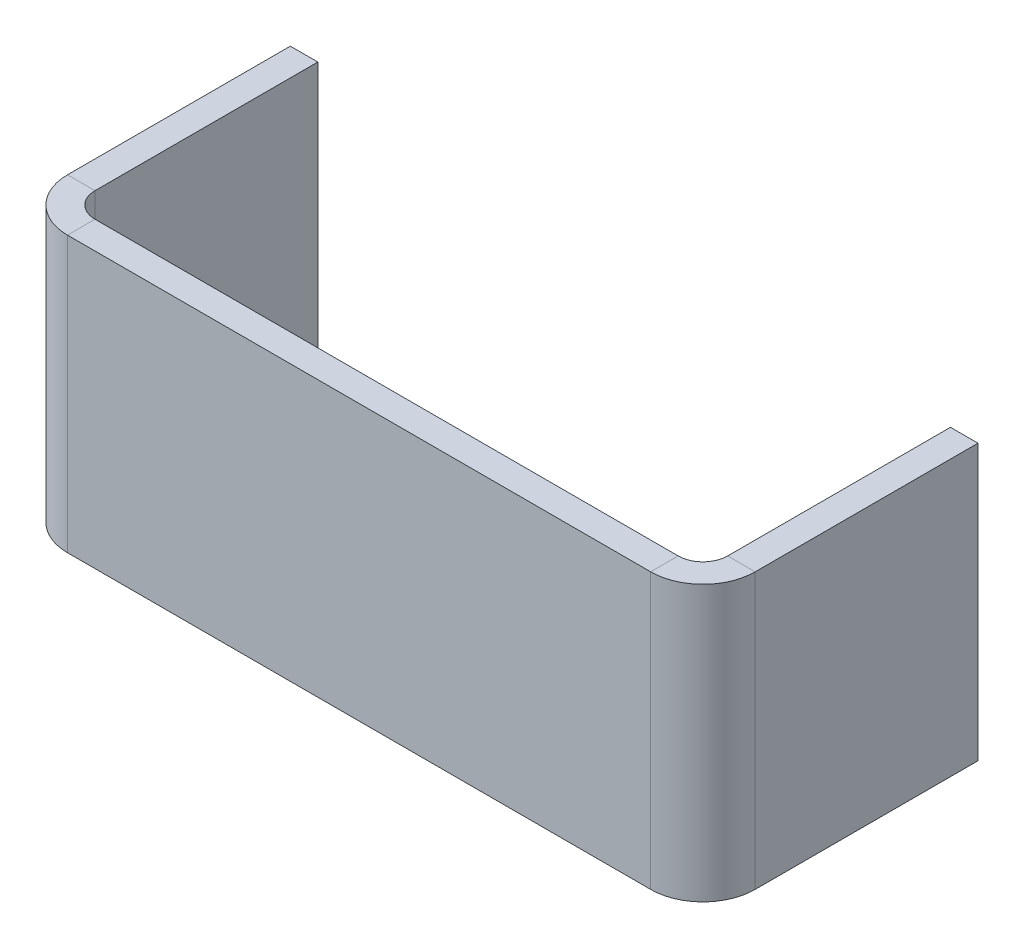
SolidWorks part; units mm, degrees
note: The reader was unsure of these and kept them because the rebuilt part matched: flange length of "Edge-Flange1".
ref_plane "Front Plane" through (0, 0, 0) normal (0, 0, 1) x (1, 0, 0)
ref_plane "Top Plane" through (0, 0, 0) normal (0, 1, 0) x (1, 0, 0)
ref_plane "Right Plane" through (0, 0, 0) normal (1, 0, 0) x (0, 0, -1)
sketch "Sketch1" plane through (0, 0, 0) normal (0, 0, 1) x (1, 0, 0)
  line L1 (-0.853, 0) -> (49.147, 0)
  line L2 (-0.853, 0) -> (-0.853, 20)
  line L3 (-0.853, 20) -> (49.147, 20)
  line L4 (49.147, 0) -> (49.147, 20)
  dimension "D1" = 50
  dimension "D2" = 20
base flange "Base-Flange1" sketch "Sketch1" thickness 2 reverse thickness direction no parameters "D1"=1.8
edge flange "Edge-Flange1" sketch "Sketch10" flange profiles "Sketch10", "Sketch11" flange angle 90 flange length 20 flange position material inside bend radius 1.8 thickness 2 relief rectangular parameters "D6"=10, "D8"=1
sketch "Sketch10" plane through (-0.853, 0, -2) normal (1, 0, 0) x (0, -1, 0)
  line L2 (-20, 0) -> (-20, 18)
  line L3 (-20, 18) -> (0, 18)
  line L4 (0, 18) -> (0, 0)
  line L5 (0, 0) -> (-20, 0) construction
  line L6 (0, 0) -> (-20, 0)
sketch "Sketch11" plane through (49.147, 0, -2) normal (-1, 0, 0) x (0, 1, 0)
  line L0 (20, 0) -> (0, 0) construction
  line L1 (20, 0) -> (0, 0)
  line L2 (20, 0) -> (20, 18)
  line L3 (20, 18) -> (0, 18)
  line L4 (0, 18) -> (0, 0)
bend "EdgeBend1" bend radius 1.8 bend angle 90 parameters "D5"=1
bend "EdgeBend2" bend radius 1.8 bend angle 90 parameters "D5"=2
sketch "Bend-Lines1" [suppressed] plane through (0, 0, 0) normal (0, 1, 0) x (1, 0, 0)
sketch "Bounding-Box1" [suppressed] plane through (0, 0, 0) normal (0, 1, 0) x (1, 0, 0)
sheet metal parameters "Sheet-Metal1" thickness 2 parameters "D1"=1.8
flat pattern "Flat-Pattern1" [suppressed]
sketch "Bend-Lines2" plane through (0, 0, 0) normal (0, 1, 0) x (1, 0, 0)
sketch3d "Bounding-Box2" [suppressed]
  line L0 (-0.853, 0, 0) -> (49.147, 0, 0) construction
  line L1 (-0.853, 20, 0) -> (49.147, 20, 0) construction
  line L2 (-0.853, 0, 0) -> (-0.853, 20, 0) construction
  line L3 (49.147, 0, 0) -> (49.147, 20, 0) construction
sheet metal parameters "Sheet-Metal2" thickness 2 parameters "D1"=1.8
flat pattern "Flat-Pattern1"
sketch "Bend-Lines2" plane through (0, 0, 0) normal (0, 0, 1) x (1, 0, 0)
  line L0 (47.5461, 0) -> (47.5461, 20) construction
  line L1 (0.7479, 20) -> (0.7479, 0) construction
  line L2 (47.5461, 0) -> (47.5461, 20) construction
  line L3 (0.7479, 20) -> (0.7479, 0) construction
sketch3d "Bounding-Box2" [suppressed]
  line L0 (-17.6512, 0, 0) -> (65.9452, 0, 0) construction
  line L1 (-17.6512, 20, 0) -> (65.9452, 20, 0) construction
  line L2 (-17.6512, 0, 0) -> (-17.6512, 20, 0) construction
  line L3 (65.9452, 0, 0) -> (65.9452, 20, 0) construction
bend of the flat pattern "Flatten-<EdgeBend1>1"
bend of the flat pattern "Flatten-<EdgeBend2>1"
